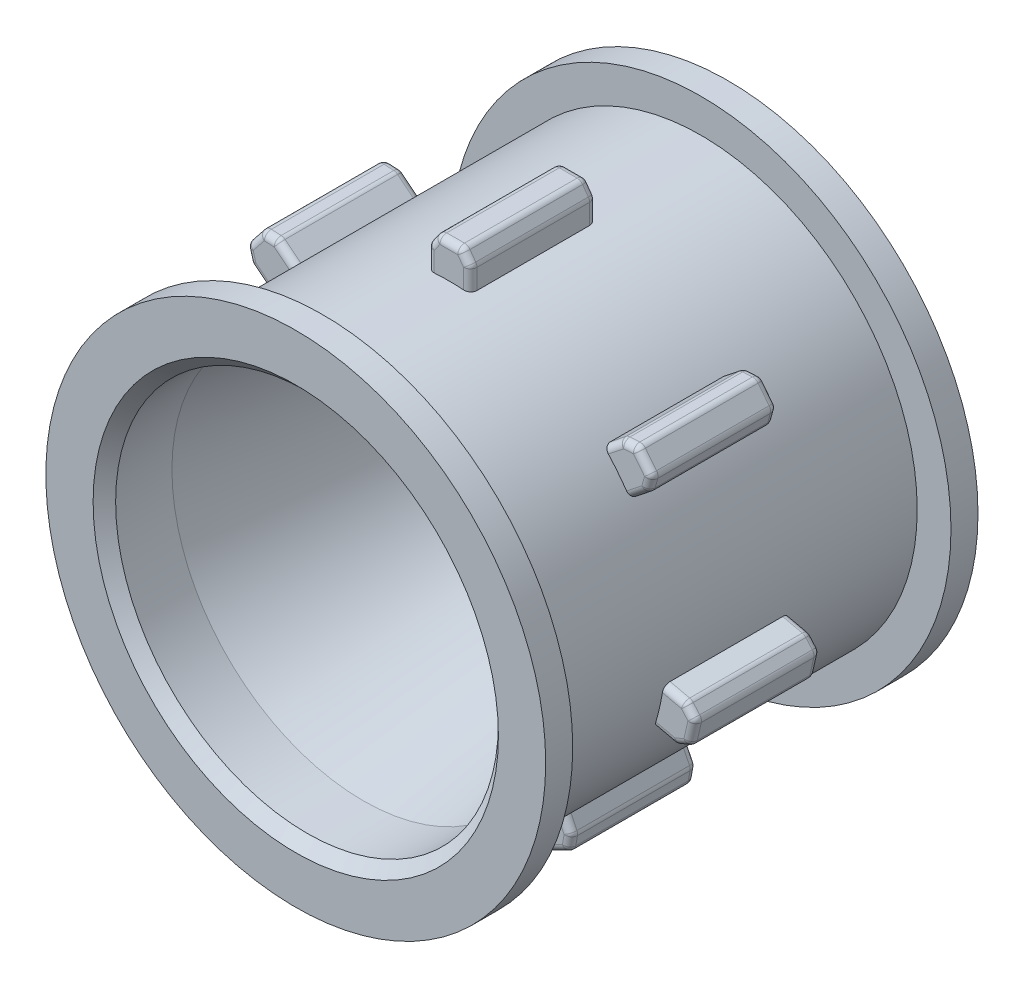
SolidWorks part; units mm, degrees
ref_plane "Ebene vorne" through (0, 0, 0) normal (0, 0, 1) x (1, 0, 0)
ref_plane "Ebene oben" through (0, 0, 0) normal (0, 1, 0) x (1, 0, 0)
ref_plane "Ebene rechts" through (0, 0, 0) normal (1, 0, 0) x (0, 0, -1)
sketch "Skizze1" plane through (0, 0, 0) normal (0, 0, 1) x (1, 0, 0)
  circle A0 centre (0, 0) radius 9.6
  dimension "D1" = 19.2
extrude "Laufrad" add sketch "Skizze1" along normal blind 8.4 and the other way blind 8.4
sketch "Skizze2" plane through (0, 0, 8.4) normal (0, 0, 1) x (1, 0, 0)
  circle A0 centre (0, 0) radius 11.1
  circle A1 centre (0, 0) radius 9.6 construction
  dimension "D1" = 1.5
extrude "Kettenführung" add sketch "Skizze2" along normal blind 1.2
mirror "Spiegeln Kettenführung" about plane through (0, 0, 0) normal (0, 0, 1) of "Kettenführung"
sketch "Skizze4" plane through (0, 0, -9.6) normal (0, 0, -1) x (-1, 0, 0)
  circle A0 centre (0, 0) radius 1
  dimension "D1" = 2
extrude "SchraubenBohrung M3" cut sketch "Skizze4" against normal through all
sketch "Skizze3" plane through (0, 0, -9.6) normal (0, 0, -1) x (-1, 0, 0)
  circle A0 centre (0, 0) radius 4.1
  dimension "D1" = 8.2
extrude "Kugellagersitz" cut sketch "Skizze3" against normal blind 2
sketch "Skizze5" plane through (0, 0, 0) normal (1, 0, 0) x (0, 0, -1)
  line L0 (-9.6, 0) -> (-9.6, 8.5)
  line L1 (-9.6, 8.5) -> (-6.6, 8.5)
  line L2 (-6.6, 8.5) -> (7.1, 6)
  line L3 (7.1, 6) -> (7.1, 0)
  line L4 (9.6, -4.1) -> (9.6, 4.1) construction
  line L5 (-9.6, 0) -> (7.6, 0) construction
  line L6 (-9.6, 0) -> (7.1, 0)
  line L7 (-9.6, 11.1) -> (-9.6, -11.1) construction
  dimension "D1" = 2.5
  dimension "D2" = 3
  dimension "D3" = 8.5
  dimension "D4" = 6
revolve "Schnitt-Rotation3" cut sketch "Skizze5" angle 360 about axis through (0, 0, -8.4) along (0, 0, 1)
chamfer "Fase1" distance 0.1 angle 45 1 edges at (-1, 0, -7.1) tangent propagation no
sketch "Skizze6" plane through (0, 0, 0) normal (0, 0, 1) x (1, 0, 0)
  line L0 (0, 0) -> (0, 10.3) construction
  line L1 (0, 10.3) -> (0, 11.1) construction
  line L2 (0.55, 11.1) -> (-0.55, 11.1)
  line L3 (-0.55, 11.1) -> (-0.95, 10.5424)
  line L4 (-0.95, 10.5424) -> (-0.95, 9.5529)
  line L5 (0.95, 10.5424) -> (0.95, 9.5529)
  line L6 (0.55, 11.1) -> (0.95, 10.5424)
  line L7 (-0.95, 9.5529) -> (0.95, 9.5529)
  circle A1 centre (0, 0) radius 9.6 construction
  dimension "D1" = 0.8
  dimension "D2" = 10.3
  dimension "D3" = 1.9
  dimension "D4" = 1.1
extrude "Zahn" add sketch "Skizze6" along normal blind 2.8 and the other way blind 2.8
fillet "Verrundung1" radius 0.3 14 edges at (0.95, 10.5424, 0) (-0.95, 10.5424, 0) (-0.95, 10.0476, -2.8) (-0.75, 10.8212, -2.8) (0, 11.1, -2.8) (0.75, 10.8212, -2.8) (0.95, 10.0476, -2.8) (-0.55, 11.1, 0) (0.55, 11.1, 0) (-0.95, 10.0476, 2.8) (-0.75, 10.8212, 2.8) (0, 11.1, 2.8) (0.75, 10.8212, 2.8) (0.95, 10.0476, 2.8)
pattern_circular "Kreismuster1" count 7 over 360 about axis through (0, 0, -8.4) along (0, 0, 1) of "Zahn", "Verrundung1"
sketch "Skizze8" plane through (0, 0, -9.6) normal (0, 0, -1) x (-1, 0, 0)
  line L0 (0, 11.1) -> (0, -11.1) construction
  line L1 (0, -11.1) -> (0, 11.1) construction
  line L2 (11.1, 0) -> (-11.1, 0) construction
  line L3 (2, 8.5) -> (2, -8.5)
  line L4 (2, -8.5) -> (-2, -8.5)
  line L5 (-2, -8.5) -> (-2, 8.5)
  line L6 (-2, 0) -> (2, 0)
  line L7 (2, 8.5) -> (-2, 8.5)
  circle A0 centre (0, 0) radius 11.1 construction
  point P12 (0, 0)
  dimension "D1" = 8.5
  dimension "D2" = 2
  dimension "D3" = 2
extrude "Auschnitt Antrieb Wage" cut sketch "Skizze8" against normal blind 2 contours L5 L6 L3 | L3 L7 L5 | L6 L5 L3 | L5 L4 L3 region at (0, 4.25, -9.6) region at (0, -4.25, -9.6)
sketch "Skizze10" plane through (0, 0, -9.6) normal (0, 0, -1) x (-1, 0, 0)
  line L0 (0, 11.1) -> (0, -11.1) construction
  line L1 (0, 10.56) -> (0, -10.56) construction
  line L2 (-8.5, 3.5) -> (8.5, 3.5)
  line L3 (8.5, 3.5) -> (8.5, -3.5)
  line L4 (8.5, -3.5) -> (-8.5, -3.5)
  line L5 (0, -3.5) -> (0, 3.5)
  line L6 (10.56, 0) -> (-10.56, 0) construction
  line L7 (-8.5, 3.5) -> (-8.5, -3.5)
  circle A0 centre (0, 0) radius 11.1 construction
  dimension "D1" = 8.5
  dimension "D2" = 3.5
  dimension "D3" = 3.5
extrude "Schnitt-Linear austragen2" cut sketch "Skizze10" against normal blind 2 contours L4 L3 L2 | L2 L7 L4 | L4 L5 L2 | L5 L4 L2 region at (4.25, 0, -9.6) region at (-4.25, 0, -9.6)
chamfer "Fase2" distance 0.5 angle 45 2 edges at (-6, 0, -7.1) (-8.5, 0, 9.6) first distance on face at (-1.1, 0, -7.1) first distance on face at (-8.5, 0, 9.6)
